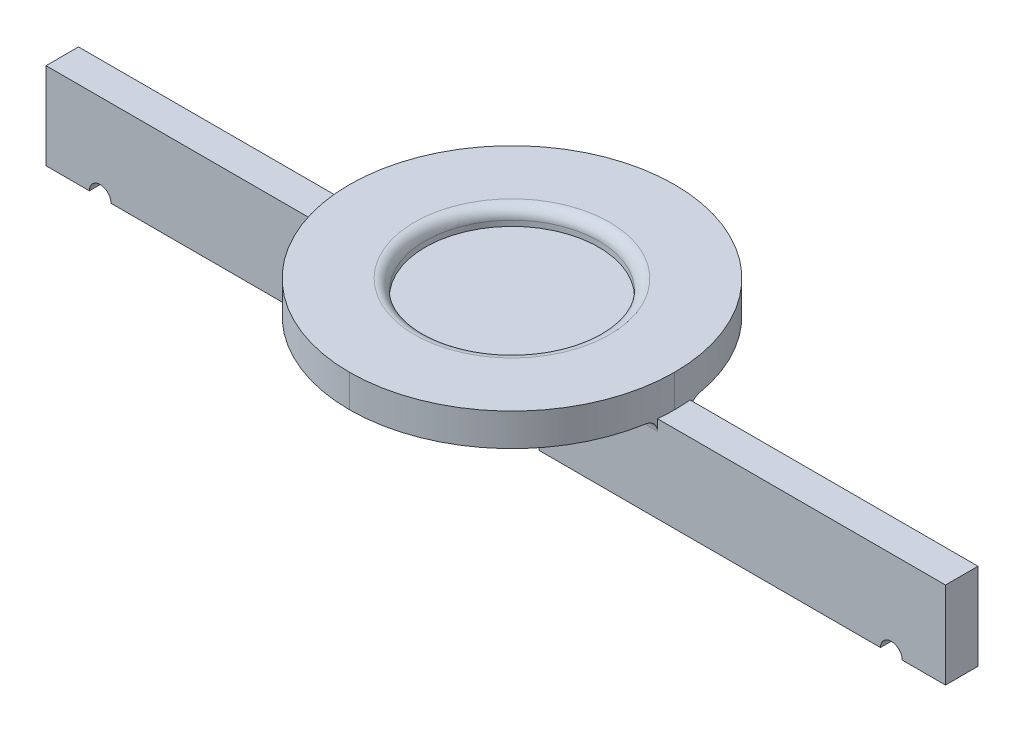
SolidWorks part; units mm, degrees
ref_plane "Front Plane" through (0, 0, 0) normal (0, 0, 1) x (1, 0, 0)
ref_plane "Top Plane" through (0, 0, 0) normal (0, 1, 0) x (1, 0, 0)
ref_plane "Right Plane" through (0, 0, 0) normal (1, 0, 0) x (0, 0, -1)
sketch "Sketch1" plane through (0, 0, 0) normal (0, 1, 0) x (1, 0, 0)
  line L1 (-15, -15) -> (15, -15)
  line L2 (-15, -15) -> (-15, 15)
  line L3 (-15, 15) -> (15, 15)
  line L4 (15, -15) -> (15, 15)
  line L5 (-15, -15) -> (15, 15) construction
  line L6 (-15, 15) -> (15, -15) construction
  point P0 (0, 0)
  dimension "D1" = 30
  dimension "D2" = 30
extrude "Boss-Extrude1" add sketch "Sketch1" along normal blind 3
sketch "Sketch2" plane through (0, 0, 0) normal (0, 0, 1) x (1, 0, 0)
  line L0 (0, 0) -> (0, -8) construction
  line L1 (-41.5, 0) -> (41.5, 0)
  line L2 (-41.5, 0) -> (-41.5, -8)
  line L3 (-41.5, -8) -> (41.5, -8)
  line L5 (41.5, 0) -> (41.5, -8)
  dimension "D1" = 83
  dimension "D2" = 8
extrude "Boss-Extrude2" add sketch "Sketch2" along normal blind 1.5 and the other way blind 1.5
sketch "Sketch4" plane through (0, 0, 1.5) normal (0, 0, 1) x (1, 0, 0)
  line L5 (-41.5, -8) -> (41.5, -8) construction
  line L7 (-37.5, -8) -> (-35.5, -8)
  line L8 (0, 0) -> (0, -8) construction
  line L9 (37.5, -8) -> (35.5, -8)
  arc A1 (-37.5, -8) -> (-35.5, -8) centre (-36.5, -8) cw
  arc A2 (37.5, -8) -> (35.5, -8) centre (36.5, -8) ccw
  line M11 (-41.5, -8) -> (41.5, -8)
  dimension "D1" = 1
  dimension "D2" = 5
extrude "Cut-Extrude1" cut sketch "Sketch4" against normal through all contours A1 M11 | A2 M11 region at (-36.5, -7.5756, 1.5) region at (36.5, -7.5756, 1.5)
sketch "Sketch5" plane through (0, 3, 0) normal (0, 1, 0) x (1, 0, 0)
  circle A0 centre (0, 0) radius 8
  dimension "D1" = 16
extrude "Cut-Extrude2" cut sketch "Sketch5" against normal blind 1.5
fillet "Fillet1" radius 1 1 edges at (0, 3, 8)
sketch "Sketch6" plane through (0, 0, 1.5) normal (0, 0, 1) x (1, 0, 0)
  circle A0 centre (0, -2) radius 1
  circle A1 centre (0, -2) radius 1 construction
extrude "Cut-Extrude3" cut sketch "Sketch6" against normal blind 10
sketch "Sketch9" plane through (0, -8, 0) normal (0, -1, 0) x (1, 0, 0)
  line L0 (15, 1.5) -> (-15, 1.5) construction
  line L1 (-4, 2) -> (4, 2)
  line L2 (-4, 2) -> (-4, 1)
  line L3 (-4, 1) -> (4, 1)
  line L4 (4, 2) -> (4, 1)
  line L5 (-4, 2) -> (4, 1) construction
  line L6 (-4, 1) -> (4, 2) construction
  line L7 (-13.6735, 0) -> (13.6735, 0)
  line L8 (-4, -1) -> (4, -2) construction
  line L9 (-4, -2) -> (4, -1) construction
  line L10 (4, -2) -> (4, -1)
  line L11 (-4, -1) -> (4, -1)
  line L12 (-4, -2) -> (-4, -1)
  line L13 (-4, -2) -> (4, -2)
  point P0 (0, 1.5)
  point P11 (0, 0)
  point P16 (0, -1.5)
  line M6 (35.5, 1.5) -> (-35.5, 1.5)
  line M8 (-35.5, -1.5) -> (35.5, -1.5)
  dimension "D1" = 8
  dimension "D2" = 1
extrude "Cut-Extrude4" cut sketch "Sketch9" against normal up to surface (8 mm away) contours L12 L10 L11 M8 | L4 L2 L3 M6 region at (0, -8, 1.25) region at (0, -8, -1.25) up to face at (0, 0, 8.25)
fillet "Fillet2" radius 1 4 edges at (-4, -4, -1) (4, -4, -1) (-4, -4, 1) (4, -4, 1)
fillet "Fillet3" radius 1 4 edges at (-9.5, 0, 1.5) (9.5, 0, 1.5) (-9.5, 0, -1.5) (9.5, 0, -1.5)
fillet "Fillet4" radius 15 4 edges at (-15, 1.5, -15) (15, 1.5, -15) (15, 1.5, 15) (-15, 1.5, 15)
